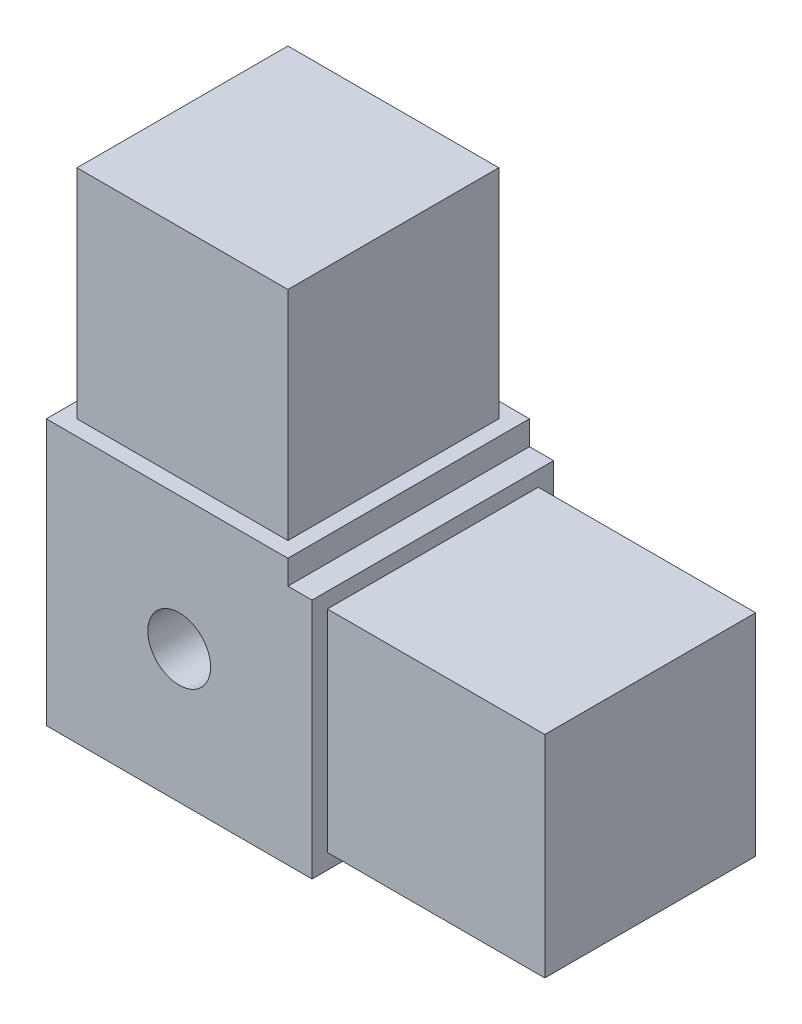
SolidWorks part; units mm, degrees
material "ALUMINUM 6061-T6"
ref_plane "Front Plane" through (0, 0, 0) normal (0, 0, 1) x (1, 0, 0)
ref_plane "Top Plane" through (0, 0, 0) normal (0, 1, 0) x (1, 0, 0)
ref_plane "Right Plane" through (0, 0, 0) normal (1, 0, 0) x (0, 0, -1)
sketch "Sketch1" plane through (0, 0, 0) normal (0, 0, 1) x (1, 0, 0)
  line L1 (-25.4, -25.4) -> (25.4, -25.4)
  line L2 (-25.4, -25.4) -> (-25.4, 25.4)
  line L3 (-25.4, 25.4) -> (25.4, 25.4)
  line L4 (25.4, -25.4) -> (25.4, 25.4)
  line L5 (-25.4, -25.4) -> (25.4, 25.4) construction
  line L6 (-25.4, 25.4) -> (25.4, -25.4) construction
  point P0 (0, 0)
  dimension "D1" = 50.8
  dimension "D2" = 50.8
extrude "Boss-Extrude1" add sketch "Sketch1" along normal mid plane 25.4
sketch "Sketch2" plane through (0, 0, 12.7) normal (0, 0, 1) x (1, 0, 0)
  line L1 (25.4, 25.4) -> (0, 25.4)
  line L2 (25.4, 25.4) -> (25.4, 0)
  line L3 (25.4, 0) -> (0, 0)
  line L4 (0, 25.4) -> (0, 0)
extrude "Cut-Extrude1" cut sketch "Sketch2" against normal through all
sketch "Sketch3" plane through (25.4, 0, 0) normal (1, 0, 0) x (0, 0, -1)
  line L0 (12.7, 0) -> (-12.7, 0) construction
  line L1 (-12.7, -25.4) -> (12.7, -25.4)
  line L2 (-12.7, -25.4) -> (-12.7, 0)
  line L3 (-12.7, 0) -> (12.7, 0)
  line L4 (12.7, -25.4) -> (12.7, 0)
  line L5 (-11.0871, -23.7871) -> (-11.0871, -1.6129)
  line L6 (-11.0871, -1.6129) -> (11.0871, -1.6129)
  line L7 (11.0871, -23.7871) -> (11.0871, -1.6129)
  line L8 (-11.0871, -23.7871) -> (11.0871, -23.7871)
  line L9 (12.7, -25.4) -> (12.7, 0) construction
  dimension "D1" = 1.6129
extrude "Cut-Extrude2" cut sketch "Sketch3" against normal blind 22.86
sketch "Sketch5" plane through (0, 25.4, 0) normal (0, 1, 0) x (1, 0, 0)
  line L0 (-1.6129, 11.0871) -> (-23.7871, 11.0871)
  line L1 (0, -12.7) -> (-25.4, -12.7)
  line L2 (0, -12.7) -> (0, 12.7)
  line L3 (0, 12.7) -> (-25.4, 12.7)
  line L4 (-25.4, -12.7) -> (-25.4, 12.7)
  line L5 (-23.7871, -11.0871) -> (-23.7871, 11.0871)
  line L6 (-1.6129, -11.0871) -> (-23.7871, -11.0871)
  line L7 (-1.6129, -11.0871) -> (-1.6129, 11.0871)
  dimension "D1" = 1.6129
extrude "Cut-Extrude4" cut sketch "Sketch5" against normal blind 22.86
sketch "Sketch7" plane through (0, 0, 12.7) normal (0, 0, 1) x (1, 0, 0)
  line L0 (-25.4, 2.54) -> (-25.4, -25.4) construction
  line L1 (-25.4, -25.4) -> (2.54, -25.4) construction
  circle A0 centre (-11.43, -11.43) radius 3.3
  dimension "D1" = 6.6
  dimension "D2" = 13.97
  dimension "D3" = 13.97
extrude "Cut-Extrude6" cut sketch "Sketch7" against normal through all
